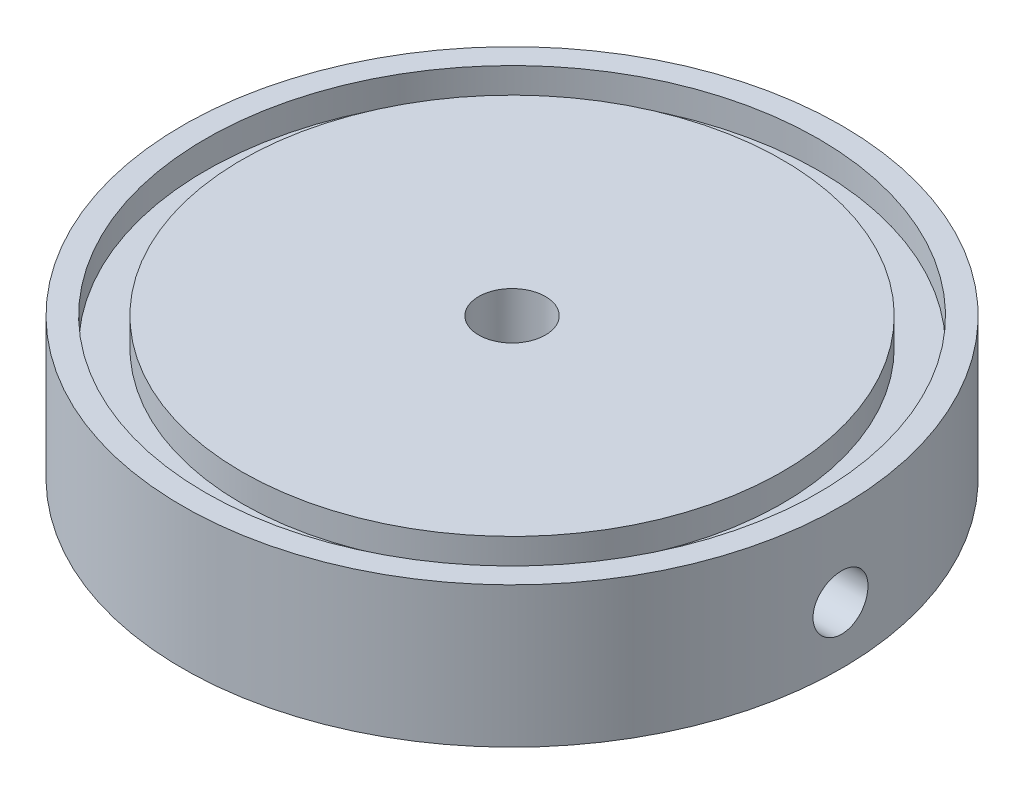
SolidWorks part; units mm, degrees
ref_plane "Front Plane" through (0, 0, 0) normal (0, 0, 1) x (1, 0, 0)
ref_plane "Top Plane" through (0, 0, 0) normal (0, 1, 0) x (1, 0, 0)
ref_plane "Right Plane" through (0, 0, 0) normal (1, 0, 0) x (0, 0, -1)
sketch "Sketch1" plane through (0, 0, 0) normal (0, 0, 1) x (1, 0, 0)
  line L0 (0, 101.6046) -> (0, 116.1639) construction
  line L1 (3.8608, 7.366) -> (38.1, 7.366)
  line L2 (3.8608, 7.366) -> (3.8608, 0)
  line L3 (10.9855, -8.89) -> (21.1455, -8.89)
  line L4 (3.8608, 0) -> (9.4615, -4.064)
  line L5 (38.1, 7.366) -> (38.1, -8.89)
  line L7 (21.1455, -8.89) -> (21.1455, -7.874)
  line L8 (21.1455, -7.874) -> (22.6695, -7.874)
  line L9 (22.6695, -7.874) -> (22.6695, -8.89)
  line L10 (22.6695, -8.89) -> (38.1, -8.89)
  line L12 (10.9855, -6.3919) -> (10.9855, -8.89)
  arc A0 (10.9855, -6.3919) -> (9.4615, -4.064) centre (8.4455, -6.3919) ccw
  dimension "D9" = 2.54
  dimension "D1" = 3.8608
  dimension "D5" = 1.524
  dimension "D6" = 1.016
  dimension "D2" = 38.1
  dimension "D4" = 7.366
  dimension "D7" = 10.9855
  dimension "D3" = 1.524
  dimension "D10" = 10.16
  dimension "D13" = 16.256
  dimension "D8" = 8.89
revolve "Revolve1" add sketch "Sketch1" angle 360 about L0
sketch "Sketch2" plane through (0, 0, 0) normal (1, 0, 0) x (0, 0, -1)
  line L0 (-38.1, -8.89) -> (38.1, -8.89) construction
  circle A0 centre (0, -2.286) radius 1.7272
  dimension "D1" = 6.604
extrude "Cut-Extrude1" cut sketch "Sketch2" along normal through all
sketch "Sketch3" plane through (0, 7.366, 0) normal (0, 1, 0) x (1, 0, 0)
  circle A0 centre (0, 0) radius 31.242
  circle A1 centre (0, 0) radius 35.433
extrude "Cut-Extrude2" cut sketch "Sketch3" against normal blind 3.175
ref_plane "Plane1" through (0, -8.89, 0) normal (0, -1, 0) x (-1, 0, 0)
sketch "Sketch4" plane through (0, -8.89, 0) normal (0, -1, 0) x (-1, 0, 0)
  line L0 (0, 0) -> (-13.97, 24.1967) construction
  circle A0 centre (-13.97, 24.1967) radius 1.0325
  circle A1 centre (0, 0) radius 27.94 construction
  dimension "D2" = 55.88
extrude "Cut-Extrude3" cut sketch "Sketch4" against normal blind 3.175
ref_axis "Axis1" through (0, 7.366, 0) along (0, -1, 0)
pattern_circular "CirPattern1" count 9 over 360 about axis through (0, 7.366, 0) along (0, -1, 0) of "Cut-Extrude3"
ref_plane "Plane2" through (38.1, 0, 0) normal (1, 0, 0) x (0, 0, -1)
ref_axis "Axis2" through (38.1, -2.286, 0) along (-1, 0, 0)
sketch "Sketch5" plane through (38.1, 0, 0) normal (1, 0, 0) x (0, 0, -1)
  circle A0 centre (0, -2.286) radius 3.175
  dimension "D1" = 6.35
extrude "Cut-Extrude4" cut sketch "Sketch5" against normal blind 9.525
fillet "Fillet1" radius 1.27 1 edges at (0, 0, -3.8608)
equation "\"ManifoldChamberThickness\"= 0.35"
equation "\"AnnulusLength\"= 0.29"
equation "\"D8@Sketch1\"=\"ManifoldChamberThickness\""
equation "\"D4@Sketch1\"=\"AnnulusLength\""
